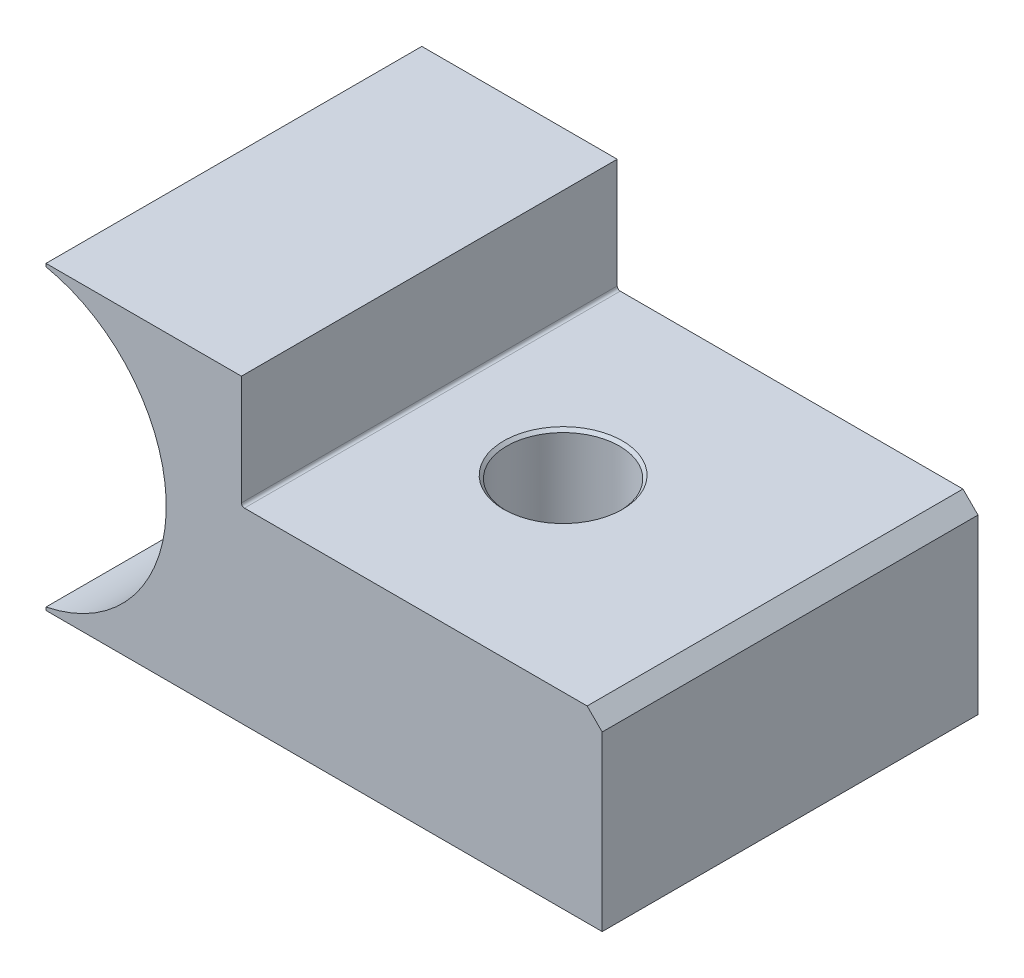
SolidWorks part; units mm, degrees
material "AISI Type A2 Tool Steel Custom"
ref_plane "Front Plane" through (0, 0, 0) normal (0, 0, 1) x (1, 0, 0)
ref_plane "Top Plane" through (0, 0, 0) normal (0, 1, 0) x (1, 0, 0)
ref_plane "Right Plane" through (0, 0, 0) normal (1, 0, 0) x (0, 0, -1)
sketch "Sketch1" plane through (0, 0, 0) normal (0, 0, 1) x (1, 0, 0)
  line L1 (2.54, 0) -> (49.53, 0)
  line L3 (2.54, 25.4) -> (19.05, 25.4)
  line L4 (49.53, 0) -> (49.53, 15.875)
  line L5 (2.54, 25.4) -> (2.54, 25.1434)
  line L6 (19.05, 25.4) -> (19.05, 15.875)
  line L7 (19.05, 15.875) -> (49.53, 15.875)
  line L8 (2.54, 0.2566) -> (2.54, 0)
  arc A1 (2.54, 0.2566) -> (2.54, 25.1434) centre (0, 12.7) ccw
  dimension "D2" = 25.4
  dimension "D1" = 16.51
  dimension "D3" = 9.525
  dimension "D4" = 2.54
  dimension "D5" = 30.48
  dimension "D6" = 15.875
  dimension "D7" = 0.2566
extrude "Boss-Extrude1" add sketch "Sketch1" along normal blind 31.75
sketch "Sketch2" plane through (0, 15.875, 0) normal (0, 1, 0) x (1, 0, 0)
  line L0 (0, -31.75) -> (0, 0) construction
  line L1 (2.54, -31.75) -> (2.54, 0) construction
  point P0 (30.353, -15.875)
  point P5 (0, -15.875)
  point P8 (2.54, -15.875)
  dimension "D1" = 30.353
hole_wizard "3/8 (0.375) Diameter Hole1" positions "Sketch2" profile "Sketch4" hole size "3/8" standard "ANSI Inch" end condition through all
sketch "Sketch4" plane through (30.353, 15.875, 15.875) normal (1, 0, 0) x (0, 0, 1)
  line L0 (0, 0) -> (0, 15.875)
  line L1 (0, 15.875) -> (4.7625, 15.875)
  line L2 (4.7625, 15.875) -> (4.7625, 0)
  line L5 (4.7625, 0) -> (0, 0)
  line L11 (0, -6.35) -> (0, 107.95) construction
  dimension "Thru Hole Dia." = 9.525
  dimension "Thru Hole Depth" = 15.875
chamfer "Chamfer1" distance 1.27 angle 45 1 edges at (49.53, 15.875, 15.875)
chamfer "Chamfer2" distance 0.254 angle 45 1 edges at (30.353, 15.875, 20.6375)
fillet "Fillet1" radius 0.254 1 edges at (19.05, 15.875, 15.875)
